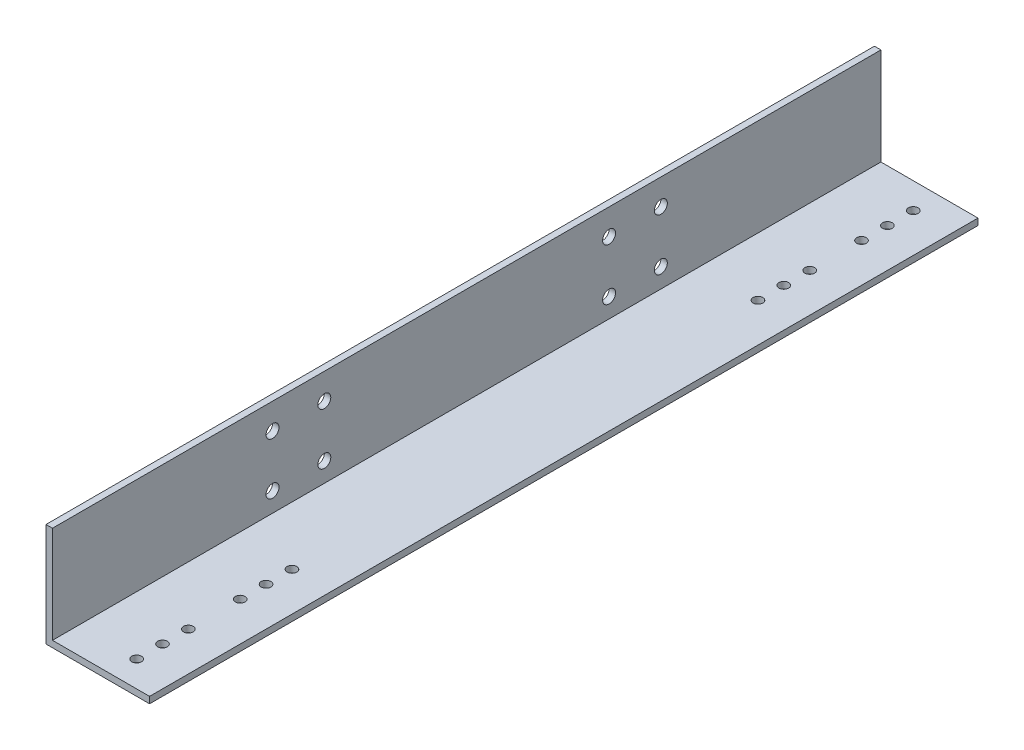
SolidWorks part; units mm, degrees
ref_plane "Front Plane" through (0, 0, 0) normal (0, 0, 1) x (1, 0, 0)
ref_plane "Top Plane" through (0, 0, 0) normal (0, 1, 0) x (1, 0, 0)
ref_plane "Right Plane" through (0, 0, 0) normal (1, 0, 0) x (0, 0, -1)
sketch "Sketch1" plane through (0, 0, 0) normal (0, 0, 1) x (1, 0, 0)
  line L0 (0, 0) -> (50.8, 0)
  line L1 (50.8, 0) -> (50.8, 3.175)
  line L2 (50.8, 3.175) -> (3.175, 3.175)
  line L3 (3.175, 3.175) -> (3.175, 50.8)
  line L4 (3.175, 50.8) -> (0, 50.8)
  line L5 (0, 50.8) -> (0, 0)
  dimension "D1" = 50.8
  dimension "D2" = 50.8
  dimension "D3" = 3.175
  dimension "D4" = 3.175
extrude "Boss-Extrude1" add sketch "Sketch1" along normal blind 406.4
sketch "Sketch2" plane through (0, 3.175, 0) normal (0, 1, 0) x (1, 0, 0)
  line L0 (50.8, -406.4) -> (3.175, -406.4) construction
  line L1 (3.175, -355.6) -> (50.8, -355.6)
  line L2 (3.175, -406.4) -> (3.175, 0) construction
  line L3 (50.8, -406.4) -> (50.8, 0) construction
  line L4 (3.175, -203.2) -> (50.8, -203.2)
  line L5 (3.175, -50.8) -> (50.8, -50.8)
  circle A0 centre (31.75, -393.7) radius 2.3813
  circle A1 centre (31.75, -381) radius 2.3813
  circle A2 centre (31.75, -368.3) radius 2.3813
  circle A3 centre (31.75, -317.5) radius 2.3813
  circle A4 centre (31.75, -330.2) radius 2.3813
  circle A5 centre (31.75, -342.9) radius 2.3813
  circle A6 centre (31.75, -12.7) radius 2.3813
  circle A7 centre (31.75, -25.4) radius 2.3813
  circle A8 centre (31.75, -38.1) radius 2.3813
  circle A9 centre (31.75, -63.5) radius 2.3813
  circle A10 centre (31.75, -76.2) radius 2.3813
  circle A11 centre (31.75, -88.9) radius 2.3813
  dimension "D1" = 4.7625
  dimension "D5" = 4.7625
  dimension "D6" = 4.7625
  dimension "D2" = 12.7
  dimension "D3" = 12.7
  dimension "D4" = 12.7
  dimension "D7" = 50.8
  dimension "D8" = 19.05
extrude "Cut-Extrude1" cut sketch "Sketch2" against normal through all contours A0 | A2 | A1 | A5 | A4 | A3 | A11 | A10 | A9 | A8 | A7 | A6 region at (31.75, 3.175, 393.7) region at (31.75, 3.175, 381) region at (31.75, 3.175, 368.3) region at (31.75, 3.175, 317.5) region at (31.75, 3.175, 330.2) region at (31.75, 3.175, 342.9) region at (31.75, 3.175, 12.7) region at (31.75, 3.175, 25.4) region at (31.75, 3.175, 38.1) region at (31.75, 3.175, 63.5) region at (31.75, 3.175, 76.2) region at (31.75, 3.175, 88.9)
sketch "Sketch3" plane through (0, 0, 0) normal (-1, 0, 0) x (0, 0, 1)
  line L0 (406.4, 50.8) -> (0, 50.8) construction
  line L1 (203.2, 50.8) -> (203.2, 0)
  line L2 (406.4, 0) -> (0, 0) construction
  circle A0 centre (107.95, 38.1) radius 3.175
  circle A1 centre (133.35, 38.1) radius 3.175
  circle A2 centre (107.95, 12.7) radius 3.175
  circle A3 centre (133.35, 12.7) radius 3.175
  circle A4 centre (273.05, 12.7) radius 3.175
  circle A5 centre (298.45, 12.7) radius 3.175
  circle A6 centre (273.05, 38.1) radius 3.175
  circle A7 centre (298.45, 38.1) radius 3.175
  point P15 (203.2, 50.8)
  dimension "D1" = 6.35
  dimension "D2" = 6.35
  dimension "D3" = 6.35
  dimension "D4" = 6.35
  dimension "D6" = 25.4
  dimension "D7" = 25.4
  dimension "D8" = 69.85
  dimension "D9" = 12.7
extrude "Cut-Extrude2" cut sketch "Sketch3" against normal through all contours A0 | A1 | A2 | A3 | A7 | A6 | A4 | A5 region at (0, 38.1, 107.95) region at (0, 38.1, 133.35) region at (0, 12.7, 107.95) region at (0, 12.7, 133.35) region at (0, 12.7, 273.05) region at (0, 12.7, 298.45) region at (0, 38.1, 273.05) region at (0, 38.1, 298.45)
equation "\"D5@Sketch2\"=\"D1@Sketch2\""
equation "\"D6@Sketch2\"=\"D1@Sketch2\""
